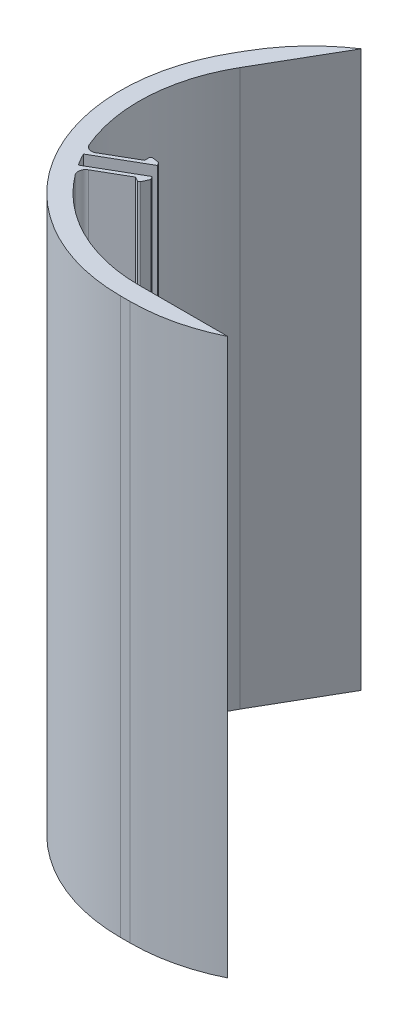
SolidWorks part; units mm, degrees
ref_plane "Front Plane" through (0, 0, 0) normal (0, 0, 1) x (1, 0, 0)
ref_plane "Top Plane" through (0, 0, 0) normal (0, 1, 0) x (1, 0, 0)
ref_plane "Right Plane" through (0, 0, 0) normal (1, 0, 0) x (0, 0, -1)
sketch "Sketch1" plane through (0, 0, 0) normal (0, 1, 0) x (1, 0, 0)
  line L0 (0, 0) -> (50, 86.6025)
  line L1 (50, 86.6025) -> (100, 0)
  line L2 (100, 0) -> (0, 0)
  dimension "D1" = 60
  dimension "D2" = 60
  dimension "D3" = 100
extrude "Boss-Extrude1" add sketch "Sketch1" along normal blind 150
fillet "Fillet1" radius 48 1 edges at (0, 75, 0)
sketch "Sketch3" plane through (0, 0, 0) normal (0, -1, 0) x (1, 0, 0)
  line L7 (45.8993, -69.5) -> (52.8868, -81.6025)
  line L8 (45.7404, -69.2247) -> (195.7404, -329.0323) construction
  line L9 (100, 0) -> (50, -86.6025) construction
  line L10 (52.8868, -81.6025) -> (97.1132, -5)
  line L11 (82.8205, -5) -> (382.8205, -5) construction
  line L12 (97.1132, -5) -> (83.1384, -5)
  arc A2 (83.1384, -5) -> (45.8993, -69.5) centre (83.1384, -48) ccw
  arc A3 (83.1384, -5) -> (45.8993, -69.5) centre (83.1384, -48) ccw
  dimension "D1" = 5
extrude "Cut-Extrude1" cut sketch "Sketch3" against normal through all both and the other way through all
sketch "Sketch4" plane through (0, 0, 0) normal (0, 1, 0) x (1, 0, 0)
  line L0 (50, 86.6025) -> (57.8868, 90.2628)
  line L1 (45.7404, 69.2247) -> (195.7404, 329.0323) construction
  line L2 (57.8868, 90.2628) -> (52.8868, 81.6025)
  line L3 (52.8868, 81.6025) -> (50, 86.6025)
  line L4 (97.1132, 5) -> (100, 0)
  line L5 (100, 0) -> (107.1132, 5)
  line L6 (82.8205, 5) -> (382.8205, 5) construction
  line L7 (107.1132, 5) -> (97.1132, 5)
  dimension "D1" = 10
  dimension "D2" = 10
extrude "Boss-Extrude2" add sketch "Sketch4" along normal up to surface (150 mm away) up to face at (64.2927, 150, -37.1194)
fillet "Fillet2" radius 48 2 edges at (50, 75, -86.6025) (100, 75, 0)
sketch "Sketch5" plane through (0, 0, 0) normal (0, 1, 0) x (1, 0, 0)
  line L0 (54.7178, 36.672) -> (57.1426, 36.3399)
  line L1 (58.8312, 27.6153) -> (57.8312, 29.3474) construction
  line L2 (57.1426, 36.3399) -> (57.6426, 35.4739)
  line L3 (54.7178, 36.672) -> (54.7178, 34.9399)
  line L4 (43.3854, 28.3972) -> (43.8503, 27.5109)
  line L5 (54.7178, 34.9399) -> (43.3854, 28.3972)
  line L6 (59.5426, 32.183) -> (60.0426, 31.317)
  line L7 (60.0426, 31.317) -> (58.9446, 28.951)
  line L8 (54.3312, 35.4096) -> (53.3312, 37.1416) construction
  line L9 (58.9446, 28.951) -> (57.4446, 29.817)
  line L10 (57.4446, 29.817) -> (45.9049, 23.1546)
  line L11 (57.6426, 35.4739) -> (43.8503, 27.5109)
  line L12 (59.5426, 32.183) -> (45.5098, 24.0812)
  line L13 (45.5098, 24.0812) -> (45.9049, 23.1546)
  line L14 (53.8883, 34.5766) -> (54.1482, 34.7266) construction
  line L15 (57.1482, 29.5304) -> (56.8883, 29.3804) construction
  dimension "D1" = 0.1
  dimension "D2" = 0.1
  dimension "D3" = 1
  dimension "D4" = 1
  dimension "D5" = 1
  dimension "D6" = 1
  dimension "D7" = 0.1
  dimension "D8" = 0.1
  dimension "D9" = 60
  dimension "D10" = 2.5
  dimension "D11" = 60
  dimension "D12" = 3
  dimension "D13" = 2.5
extrude "Boss-Extrude3" add sketch "Sketch5" along normal up to surface (150 mm away) up to face at (63.4226, 150, -36.617)
fillet "Fillet3" radius 2 2 edges at (47.4341, 75, -24.0375) (44.5341, 75, -29.0604)
fillet "Fillet4" radius 0.5 2 edges at (54.7178, 75, -36.672) (58.9446, 75, -28.951)
